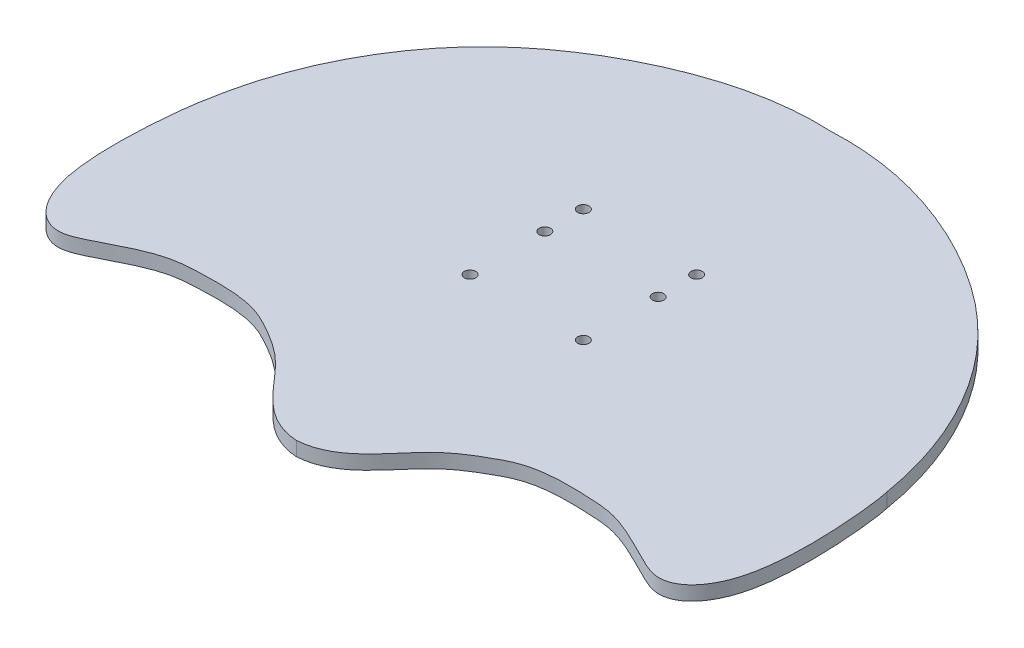
SolidWorks part; units mm, degrees
material "6061-T6 (SS)"
ref_plane "Front Plane" through (0, 0, 0) normal (0, 0, 1) x (1, 0, 0)
ref_plane "Top Plane" through (0, 0, 0) normal (0, 1, 0) x (1, 0, 0)
ref_plane "Right Plane" through (0, 0, 0) normal (1, 0, 0) x (0, 0, -1)
sketch "Sketch3" plane through (0, 0, 0) normal (0, 1, 0) x (1, 0, 0)
  line L0 (0, 0) -> (0, 159.1899) construction
  line L1 (0, 0) -> (0, -140.5301) construction
  line L2 (0, 0) -> (-190.5, 0) construction
  line L3 (0, 0) -> (190.5, 0) construction
  spline S0 degree 3 poles (-190.5, 0) (-184.3927, 37.537) (-157.2613, 93.9641) (-82.3875, 146.6227) (-31.3114, 160.7999) (0, 159.1899) knots 0 0 0 0 0.424401 0.65637 1 1 1 1
  spline S1 degree 3 poles (-190.5, 0) (-192.064, -4.9635) (-201.9672, -83.3146) (-174.6966, -109.29) (-151.6301, -100.568) (-131.4108, -87.7198) (-96.8436, -85.3754) (-78.6925, -86.2588) (-58.8335, -96.8794) (-37.3059, -109.9358) (-21.3496, -139.1148) (0, -140.5301) knots 0 0 0 0 0.166997 0.292321 0.319633 0.426735 0.458914 0.609242 0.64191 0.766802 1 1 1 1
  spline S2 degree 3 poles (190.5, 0) (192.064, -4.9635) (201.9672, -83.3146) (174.6966, -109.29) (151.6301, -100.568) (131.4108, -87.7198) (96.8436, -85.3754) (78.6925, -86.2588) (58.8335, -96.8794) (37.3059, -109.9358) (21.3496, -139.1148) (0, -140.5301) knots 0 0 0 0 0.166997 0.292321 0.319633 0.426735 0.458914 0.609242 0.64191 0.766802 1 1 1 1
  spline S3 degree 3 poles (190.5, 0) (184.3927, 37.537) (157.2613, 93.9641) (82.3875, 146.6227) (31.3114, 160.7999) (0, 159.1899) knots 0 0 0 0 0.424401 0.65637 1 1 1 1
  dimension "D1" = 381
  dimension "D2" = 299.72
  dimension "D3" = 159.1899
  dimension "D4" = 86.8953
  dimension "D5" = 104.4979
  dimension "D6" = 29.1616
  dimension "D7" = 92.2742
  dimension "D8" = 108.411
  dimension "D9" = 67.4883
  dimension "D10" = 43.7314
  dimension "D11" = 117.6915
  dimension "D12" = 162.2568
  dimension "D13" = 89.4522
  dimension "D14" = 140.1036
  dimension "D15" = 175.0666
  dimension "D16" = 50.2669
  dimension "D17" = 101.3666
  dimension "D18" = 138.1225
  dimension "D19" = 155.1557
  dimension "D20" = 192.0074
  dimension "D21" = 193.9268
  dimension "D23" = 76.6666
extrude "Boss-Extrude1" add sketch "Sketch3" along normal blind 7.9502 from surface starting at plane "Top Plane"
sketch "Sketch5" plane through (0, 0, 0) normal (0, -1, 0) x (1, 0, 0)
  line L0 (0, 0) -> (0, -20.32) construction
  line L1 (31.75, -52.07) -> (-31.75, -52.07)
  line L2 (31.75, -52.07) -> (31.75, 11.43)
  line L3 (31.75, 11.43) -> (-31.75, 11.43)
  line L4 (-31.75, -52.07) -> (-31.75, 11.43)
  line L5 (31.75, -52.07) -> (-31.75, 11.43) construction
  line L6 (31.75, 11.43) -> (-31.75, -52.07) construction
  line L7 (-31.75, -52.07) -> (-31.75, -30.48)
  line L8 (-31.75, -30.48) -> (31.75, -30.48) construction
  point P0 (0, -20.32)
  point P3 (0, -20.32)
  dimension "D2" = 63.5
  dimension "D3" = 63.5
  dimension "D4" = 21.59
hole_wizard "1/4 (0.25) Diameter Hole1" positions "Sketch6" profile "Sketch7" hole size "1/4" standard "ANSI Inch" end condition through all
sketch "Sketch6" plane through (0, 0, 0) normal (0, -1, 0) x (-1, 0, 0)
  point P0 (-31.75, 52.07)
  point P3 (31.75, 52.07)
  point P6 (31.75, -11.43)
  point P9 (-31.75, -11.43)
  point P12 (-31.75, 30.48)
  point P15 (31.75, 30.48)
sketch "Sketch7" plane through (31.75, 0, -52.07) normal (1, 0, 0) x (0, 0, -1)
  line L0 (0, 0) -> (0, 7.9502)
  line L1 (0, 7.9502) -> (3.175, 7.9502)
  line L2 (3.175, 7.9502) -> (3.175, 0)
  line L5 (3.175, 0) -> (0, 0)
  line L11 (0, -6.35) -> (0, 107.95) construction
  dimension "Thru Hole Dia." = 6.35
  dimension "Thru Hole Depth" = 7.9502
sketch "Sketch9" [suppressed] plane through (0, 7.9502, 0) normal (0, 1, 0) x (1, 0, 0)
  line L0 (102.3823, -86.0787) -> (102.3823, 130.9193)
  line L1 (-50.7649, -102.4301) -> (50.7649, -102.4301)
  spline S0 degree 3 poles (0, -140.5301) (21.3496, -139.1148) (37.3059, -109.9358) (58.8335, -96.8794) (78.6925, -86.2588) (96.8436, -85.3754) (131.4108, -87.7198) (151.6301, -100.568) (174.6966, -109.29) (201.9672, -83.3146) (192.064, -4.9635) (190.5, 0) knots 0 0 0 0 0.233198 0.35809 0.390758 0.541086 0.573265 0.680367 0.707679 0.833003 1 1 1 1 construction
  spline S1 degree 3 poles (190.5, 0) (184.3927, 37.537) (157.2613, 93.9641) (82.3875, 146.6227) (31.3114, 160.7999) (0, 159.1899) knots 0 0 0 0 0.424401 0.65637 1 1 1 1 construction
  spline S2 degree 3 poles (-190.5, 0) (-192.064, -4.9635) (-201.9672, -83.3146) (-174.6966, -109.29) (-151.6301, -100.568) (-131.4108, -87.7198) (-96.8436, -85.3754) (-78.6925, -86.2588) (-58.8335, -96.8794) (-37.3059, -109.9358) (-21.3496, -139.1148) (0, -140.5301) knots 0 0 0 0 0.166997 0.292321 0.319633 0.426735 0.458914 0.609242 0.64191 0.766802 1 1 1 1 construction
  dimension "D1" = 38.1
split line "Split Line1" [suppressed]
equation "\"Plate thickness\"=0.313"
equation "\"D1@Boss-Extrude1\"=\"Plate thickness\""
equation "\"Bracket Alignment\"= .80"
equation "\"D1@Sketch5\"=\"Bracket Alignment\""
